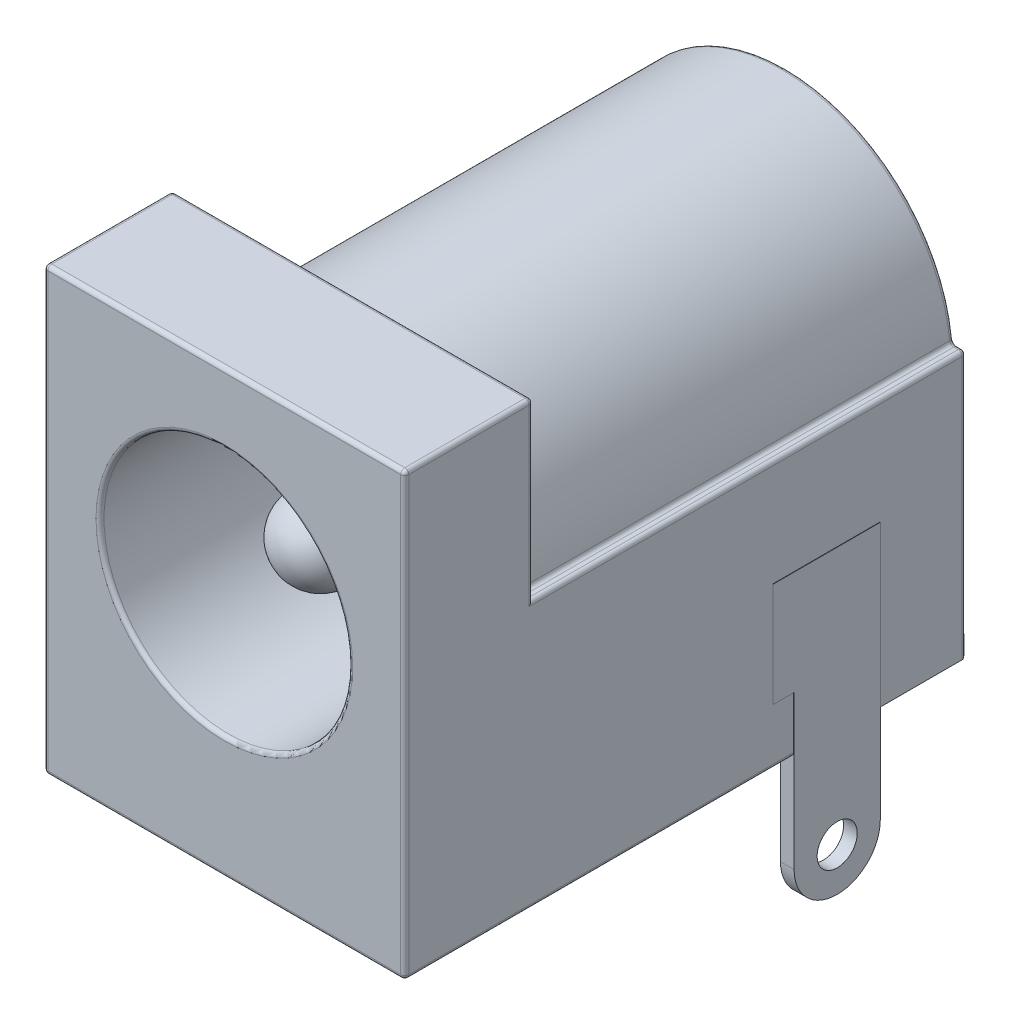
SolidWorks part; units mm, degrees
ref_plane "Front Plane" through (0, 0, 0) normal (0, 0, 1) x (1, 0, 0)
ref_plane "Top Plane" through (0, 0, 0) normal (0, 1, 0) x (1, 0, 0)
ref_plane "Right Plane" through (0, 0, 0) normal (1, 0, 0) x (0, 0, -1)
sketch "Sketch1" plane through (0, 0, 0) normal (0, 0, 1) x (1, 0, 0)
  line L1 (-4.5, 5.5) -> (4.5, 5.5)
  line L2 (-4.5, 5.5) -> (-4.5, -5.5)
  line L3 (-4.5, -5.5) -> (4.5, -5.5)
  line L4 (4.5, 5.5) -> (4.5, -5.5)
  line L5 (-4.5, 5.5) -> (4.5, -5.5) construction
  line L6 (-4.5, -5.5) -> (4.5, 5.5) construction
  circle A0 centre (0, 0.65) radius 3.1
  point P0 (0, 0)
  dimension "D3" = 4.85
  dimension "D4" = 6.2
  dimension "D1" = 9
  dimension "D2" = 11
extrude "Boss-Extrude1" add sketch "Sketch1" against normal blind 14
sketch "Sketch2" plane through (0, 0, -14) normal (0, 0, -1) x (-1, 0, 0)
  line L2 (0, 5) -> (3.0104, 5) construction
  line L3 (-4.5, 5.5) -> (4.5, 5.5) construction
  line L4 (4.5, 5.5) -> (4.5, -5.5) construction
  line L5 (-4.5, 5.5) -> (4.5, 5.5)
  line L6 (-4.2, 1.15) -> (4.2, 1.15) construction
  line L7 (4.5, -5.5) -> (-4.5, -5.5) construction
  line L8 (-4.2, 1.15) -> (-4.5, 1.15)
  line L9 (-4.5, -5.5) -> (-4.5, 5.5) construction
  line L10 (-4.5, 1.15) -> (-4.5, 5.5)
  line L11 (4.5, 5.5) -> (4.5, 1.15)
  line L12 (4.5, 1.15) -> (4.2, 1.15)
  arc A0 (-4.2, 1.15) -> (4.2, 1.15) centre (0, 0.7841) cw
  point P14 (0, 1.15)
  dimension "D1" = 0.5
  dimension "D2" = 6.65
  dimension "D3" = 0.3
extrude "Cut-Extrude1" cut sketch "Sketch2" against normal offset from surface (10.8 mm away) 3.2 up to face at (3.1, 0.65, 0)
sketch "Sketch3" plane through (0, 0, -14) normal (0, 0, -1) x (-1, 0, 0)
  line L0 (-4.5, 1.15) -> (-4.5, -5.5)
  line L1 (-4.5, -5.5) -> (4.5, -5.5)
  line L2 (4.5, -5.5) -> (4.5, 1.15)
  line L3 (4.5, 1.15) -> (4.2, 1.15)
  line L4 (-4.5, 1.15) -> (-4.2, 1.15)
  arc A0 (-4.2, 1.15) -> (4.2, 1.15) centre (0, 0.7841) cw
  arc A1 (4.2, 1.15) -> (-4.2, 1.15) centre (0, 0.7841) ccw construction
extrude "Boss-Extrude2" add sketch "Sketch3" against normal blind 1
sketch "Sketch4" plane through (0, 0, -13) normal (0, 0, 1) x (1, 0, 0)
  circle A0 centre (0, 0.65) radius 1
  circle A1 centre (0, 0.65) radius 3.1 construction
  dimension "D1" = 2
extrude "Boss-Extrude3" add sketch "Sketch4" along normal offset from surface (11.6 mm away) 1.4 up to face at (3.1, 0.65, 0)
fillet "Fillet1" radius 1 1 edges at (1, 0.65, -1.4)
sketch "Sketch5" plane through (0, 0, -14) normal (0, 0, -1) x (-1, 0, 0)
  line L0 (1.5, 2.4729) -> (-1.5, 2.4729)
  line L1 (-1.5, -0.1729) -> (-1.5, -4.35)
  line L2 (-1.35, -4.5) -> (-1.315, -4.5)
  line L3 (-1.165, -4.65) -> (-1.165, -7.835)
  line L4 (1.5, -0.1729) -> (1.5, -4.35)
  line L5 (1.35, -4.5) -> (1.315, -4.5)
  line L6 (1.165, -4.65) -> (1.165, -7.835)
  line L7 (4.5, -5.5) -> (-4.5, -5.5) construction
  arc A0 (-1.5, 2.4729) -> (-1.5, -0.1729) centre (0, 1.15) ccw
  arc A1 (-1.165, -7.835) -> (1.165, -7.835) centre (0, -7.835) ccw
  circle A2 centre (0, -7.835) radius 0.5
  arc A3 (1.5, -0.1729) -> (1.5, 2.4729) centre (0, 1.15) ccw
  arc A4 (1.315, -4.5) -> (1.165, -4.65) centre (1.315, -4.65) ccw
  arc A5 (1.5, -4.35) -> (1.35, -4.5) centre (1.35, -4.35) cw
  arc A6 (-1.315, -4.5) -> (-1.165, -4.65) centre (-1.315, -4.65) cw
  arc A7 (-1.35, -4.5) -> (-1.5, -4.35) centre (-1.35, -4.35) cw
  dimension "D1" = 1
  dimension "D3" = 4
  dimension "D7" = 0.15
  dimension "D2" = 2.33
  dimension "D4" = 1
  dimension "D5" = 2.335
  dimension "D6" = 3
extrude "Boss-Extrude4" add sketch "Sketch5" along normal blind 0.01 and the other way blind 0.33
sketch "Sketch6" plane through (4.5, 0, 0) normal (1, 0, 0) x (0, 0, -1)
  line L0 (11.85, -7.925) -> (11.85, -1.5)
  line L1 (11.85, -1.5) -> (9.18, -1.5)
  line L2 (9.18, -1.5) -> (9.18, -4.1)
  line L3 (9.18, -4.1) -> (9.7, -4.1)
  line L4 (9.7, -4.1) -> (9.7, -7.925)
  line L5 (13.67, -9) -> (14.01, -9) construction
  line L6 (14, -5.5) -> (14, 1.15) construction
  line L7 (14, -5.5) -> (0, -5.5) construction
  arc A0 (9.7, -7.925) -> (11.85, -7.925) centre (10.775, -7.925) ccw
  circle A1 centre (10.775, -7.925) radius 0.5
  dimension "D1" = 2.15
  dimension "D6" = 1
  dimension "D2" = 2.15
  dimension "D3" = 2.67
  dimension "D4" = 2.6
  dimension "D5" = 1.4
extrude "Boss-Extrude5" add sketch "Sketch6" along normal blind 0.01 and the other way blind 0.33
ref_plane "Plane1" through (0, 0, -7.2) normal (0, 0, -1) x (-1, 0, 0)
sketch "Sketch8" plane through (0, 0, -7.2) normal (0, 0, -1) x (-1, 0, 0)
  line L0 (-1.165, -5.5) -> (1.165, -5.5)
  line L1 (1.165, -5.5) -> (1.165, -7.835)
  line L2 (-1.165, -5.5) -> (-1.165, -7.835)
  arc A0 (1.165, -7.835) -> (-1.165, -7.835) centre (0, -7.835) cw
  arc A1 (-1.165, -7.835) -> (1.165, -7.835) centre (0, -7.835) ccw construction
  circle A2 centre (0, -7.835) radius 0.5
  circle A3 centre (0, -7.835) radius 0.5 construction
extrude "Boss-Extrude6" add sketch "Sketch8" along normal blind 0.33
fillet "Fillet2" radius 0.1 24 edges at (4.35, 1.15, -14) (-4.35, 1.15, -14) (3.1, 0.65, 0) (4.5, 3.325, -3.2) (-4.5, 3.325, -3.2) (-4.5, -2.175, -14) (-2.8325, -5.5, -14) (2.8325, -5.5, -14) (4.5, -2.175, -14) (4.5, 1.15, -8.6) (4.2, 1.15, -8.6) (-4.2, 1.15, -8.6) (-4.5, 1.15, -8.6) (0, 5, -3.2) (0, 5, -14) (0, 5.5, -3.2) (0, 5.5, 0) (4.5, 0, 0) (-4.5, 0, 0) (-4.5, -5.5, -7) (0, -5.5, 0) (4.5, -5.5, -4.85) (-4.5, 5.5, -1.6) (4.5, 5.5, -1.6)
